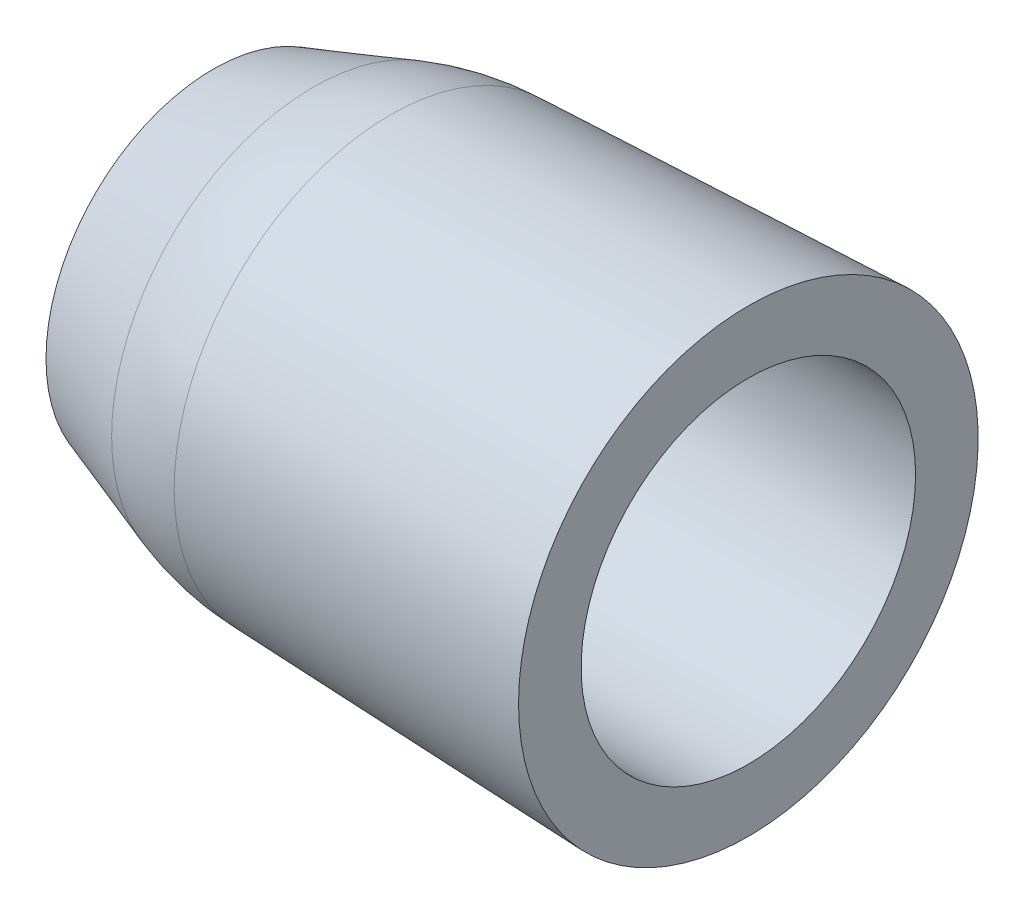
SolidWorks part; units mm, degrees
ref_plane "Front Plane" through (0, 0, 0) normal (0, 0, 1) x (1, 0, 0)
ref_plane "Top Plane" through (0, 0, 0) normal (0, 1, 0) x (1, 0, 0)
ref_plane "Right Plane" through (0, 0, 0) normal (1, 0, 0) x (0, 0, -1)
sketch "Sketch2" plane through (0, 0, 0) normal (0, 0, 1) x (1, 0, 0)
  line L0 (-27.8095, 0) -> (-2.4095, 0) construction
  line L1 (-2.4095, 10.9078) -> (-21.2812, 10.1867)
  line L2 (-21.2812, 10.1867) -> (-27.8095, 7.9375)
  line L3 (-27.8095, 7.9375) -> (-27.8095, 0)
  line L4 (-2.4095, 10.9078) -> (-2.4095, 0)
  line L5 (-27.8095, 0) -> (-2.4095, 0)
  line L6 (-27.8095, 0) -> (-2.4095, 0)
  dimension "D1" = 7.9375
  dimension "D2" = 25.4
revolve "Revolve1" add sketch "Sketch2" angle 360 about L0 region at (-14.6414, 5.1104, 0)
sketch "Sketch3" plane through (-2.4095, 0, 0) normal (1, 0, 0) x (0, 0, -1)
  circle A0 centre (0, 0) radius 7.9375
  dimension "D1" = 15.875
extrude "Cut-Extrude1" cut sketch "Sketch3" against normal blind 25.146
fillet "Fillet1" radius 12.7 1 edges at (-21.2812, 0, 10.1867)
sketch "Sketch4" plane through (-27.5555, 0, 0) normal (1, 0, 0) x (0, 0, -1)
  circle A0 centre (-2.4877, 4.1156) radius 1.1723
